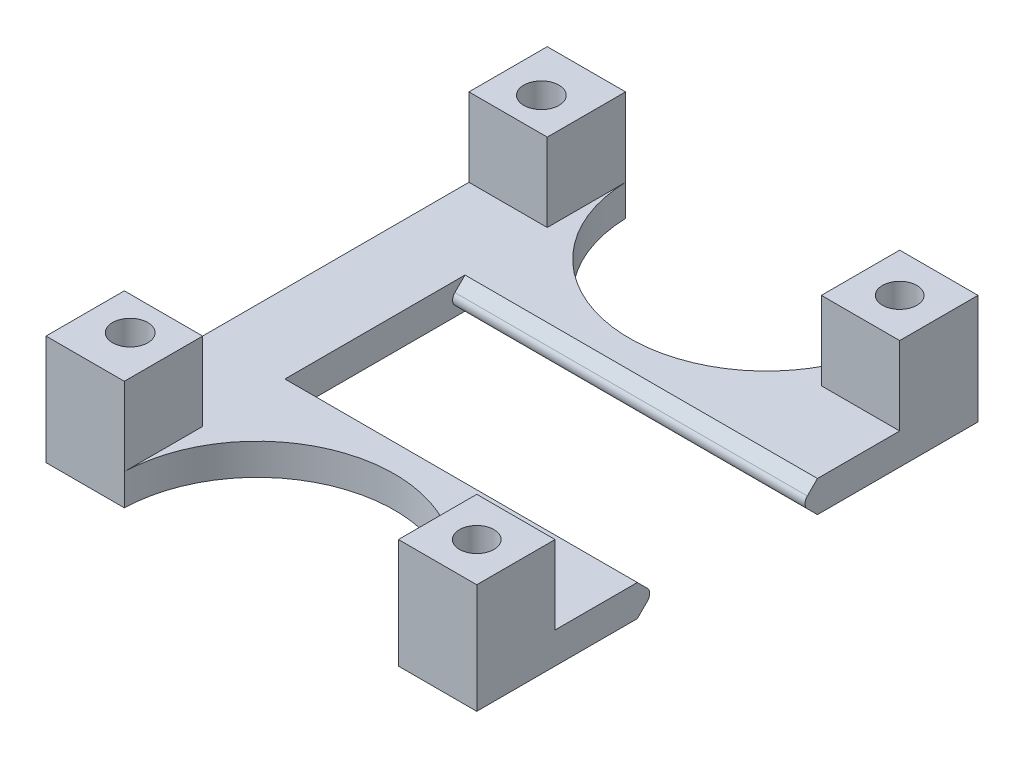
SolidWorks part; units mm, degrees
ref_plane "Front Plane" through (0, 0, 0) normal (0, 0, 1) x (1, 0, 0)
ref_plane "Top Plane" through (0, 0, 0) normal (0, 1, 0) x (1, 0, 0)
ref_plane "Right Plane" through (0, 0, 0) normal (1, 0, 0) x (0, 0, -1)
sketch "Sketch1" plane through (0, 0, 0) normal (0, 1, 0) x (1, 0, 0)
  line L0 (10, 10) -> (10, -10)
  line L2 (0, -20) -> (0, 20)
  line L4 (55, -20) -> (55, 20) construction
  line L5 (10, -10) -> (45, -10)
  line L6 (45, -10) -> (45, 10) construction
  line L7 (45, 10) -> (10, 10)
  line L8 (45, 10) -> (55, 10)
  line L11 (55, 10) -> (55, 20)
  line L13 (27.5, -20) -> (27.5, -10) construction
  line L14 (27.5, 10) -> (27.5, 20) construction
  line L16 (45, -10) -> (55, -10)
  line L17 (55, -20) -> (55, -10)
  line L18 (55, -20) -> (55, -32)
  line L19 (55, -32) -> (45, -32)
  line L21 (55, 20) -> (55, 32)
  line L22 (55, 32) -> (45, 32)
  line L24 (0, -20) -> (0, -32)
  line L27 (0, 20) -> (0, 32)
  line L30 (-55, 0) -> (55, 0) construction
  line L31 (0, 0) -> (55, 0) construction
  line L32 (10, -32) -> (0, -32)
  line L34 (10, 32) -> (0, 32)
  arc A26 (45, -32) -> (10, -32) centre (27.5, -32.5074) ccw
  arc A27 (45, 32) -> (10, 32) centre (27.5, 32.5074) cw
  circle A46 centre (50, 27) radius 2.2
  circle A47 centre (50, -27) radius 2.2
  circle A49 centre (5, -26.25) radius 2.2479 construction
  circle A50 centre (5, -26.25) radius 2.2479
  circle A51 centre (5, 26.25) radius 2.2479 construction
  circle A52 centre (5, 26.25) radius 2.2479
  point P30 (27.5, -15)
  point P35 (27.5, 15)
  point P36 (27.5, -10)
  point P39 (0, 0)
  dimension "D18" = 4.4
  dimension "D1" = 40
  dimension "D2" = 55
  dimension "D24" = 10
  dimension "D13" = 5
  dimension "D16" = 5
  dimension "D7" = 10
  dimension "D9" = 5
  dimension "D14" = 5
  dimension "D4" = 20
  dimension "D5" = 10
  dimension "D3" = 10
  dimension "D6" = 35
  dimension "D8" = 12
  dimension "D10" = 10
extrude "Extrude-Body" add sketch "Sketch1" along normal blind 4 contours L4 L2 A47 A46 L7 L6 L5 L0 | L19 L18 A47 | L22 L21 A46 | L27 | L24 region at (9.1561, 0, 0)
sketch "Sketch5" plane through (0, 4, 0) normal (0, 1, 0) x (1, 0, 0)
  line L6 (10, -32) -> (0, -32) construction
  line L9 (45, -22) -> (55, -22)
  line L21 (55, -22) -> (55, -32)
  line L23 (0, -32) -> (0, 32) construction
  line L34 (10, 32) -> (0, 32) construction
  line L36 (55, -32) -> (45, -32)
  line L37 (45, -32) -> (45, -22)
  line L38 (55, 22) -> (55, 32)
  line L39 (55, 32) -> (45, 32)
  line L41 (45, 32) -> (45, 22)
  line L42 (45, 22) -> (55, 22)
  line L43 (10, 22) -> (10, 32)
  line L44 (10, 32) -> (0, 32)
  line L46 (0, 32) -> (0, 22)
  line L47 (0, -32) -> (0, 32) construction
  line L48 (0, 22) -> (10, 22)
  line L49 (10, -22) -> (0, -22)
  line L50 (0, -22) -> (0, -32)
  line L51 (0, -32) -> (10, -32)
  line L52 (10, -32) -> (10, -22)
  circle A0 centre (50, 27) radius 2.2
  circle A3 centre (50, -27) radius 2.2
  circle A11 centre (50, 27) radius 2.2 construction
  circle A12 centre (50, -27) radius 2.2 construction
  circle A13 centre (5, 26.25) radius 2.2479 construction
  circle A14 centre (5, 26.25) radius 2.2479
  circle A15 centre (5, -26.25) radius 2.2479 construction
  circle A16 centre (5, -26.25) radius 2.2479
  dimension "D1" = 10
  dimension "D2" = 10
  dimension "D3" = 10
  dimension "D4" = 10
  dimension "D5" = 10
  dimension "D6" = 10
  dimension "D8" = 10
extrude "Extrude-Legs" add sketch "Sketch5" along normal blind 10
sketch "Sketch6" plane through (0, 4, 0) normal (0, 1, 0) x (1, 0, 0)
  line L0 (55, -10) -> (55, -22) construction
  line L1 (10, -10) -> (55, -10)
  line L2 (10, -10) -> (10, -9.5)
  line L3 (10, -9.5) -> (55, -9.5)
  line L4 (55, -10) -> (55, -9.5)
  line L5 (10, 10) -> (55, 10)
  line L6 (10, 10) -> (10, 9.5)
  line L7 (10, 9.5) -> (55, 9.5)
  line L8 (55, 10) -> (55, 9.5)
  line L9 (55, 10) -> (55, 22) construction
  dimension "D1" = 19
extrude "Boss-Extrude1" add sketch "Sketch6" against normal up to surface (4 mm away) up to face at (5, 0, -24.0021)
sketch "Sketch7" plane through (55, 0, 0) normal (1, 0, 0) x (0, 0, -1)
  line L0 (-10.2071, 2.7071) -> (-11.5, 4)
  line L1 (-9.5, 0) -> (-9.5, 4) construction
  line L2 (-9.5, 4) -> (-22, 4) construction
  line L3 (-10.2071, 1.2929) -> (-11.5, 0)
  line L4 (-9.5, 0) -> (-32, 0) construction
  line L5 (10.2071, 2.7071) -> (11.5, 4)
  line L6 (9.5, 0) -> (9.5, 4) construction
  line L7 (9.5, 4) -> (22, 4) construction
  line L8 (10.2071, 1.2929) -> (11.5, 0)
  line L9 (9.5, 0) -> (32, 0) construction
  line L10 (11.5, 4) -> (9.5, 4)
  line L11 (9.5, 0) -> (9.5, 4) construction
  line L12 (9.5, 4) -> (9.5, 0)
  line L13 (9.5, 0) -> (11.5, 0)
  line L14 (-11.5, 4) -> (-9.5, 4)
  line L15 (-9.5, 4) -> (-9.5, 0)
  line L16 (-9.5, 0) -> (-11.5, 0)
  line L17 (0, 0) -> (0, 8.2974) construction
  arc A0 (10.2071, 2.7071) -> (10.2071, 1.2929) centre (10.9142, 2) ccw
  arc A1 (-10.2071, 2.7071) -> (-10.2071, 1.2929) centre (-10.9142, 2) cw
  point P36 (9.5, 2)
  point P39 (-9.5, 2)
  dimension "D3" = 1
  dimension "D1" = 45
  dimension "D2" = 45
extrude "Cut-Extrude1" cut sketch "Sketch7" against normal up to surface (45 mm away) up to face at (10, 2, 0)
equation "\"boltdiameter\"=4.4"
equation "\"D18@Sketch1\"=\"boltdiameter\""
equation "\"boltfacediameter\"=7"
equation "\"insetNutFlat\"=8.4"
equation "\"screwInset\"=8.43"
equation "\"slotLength\"=80"
